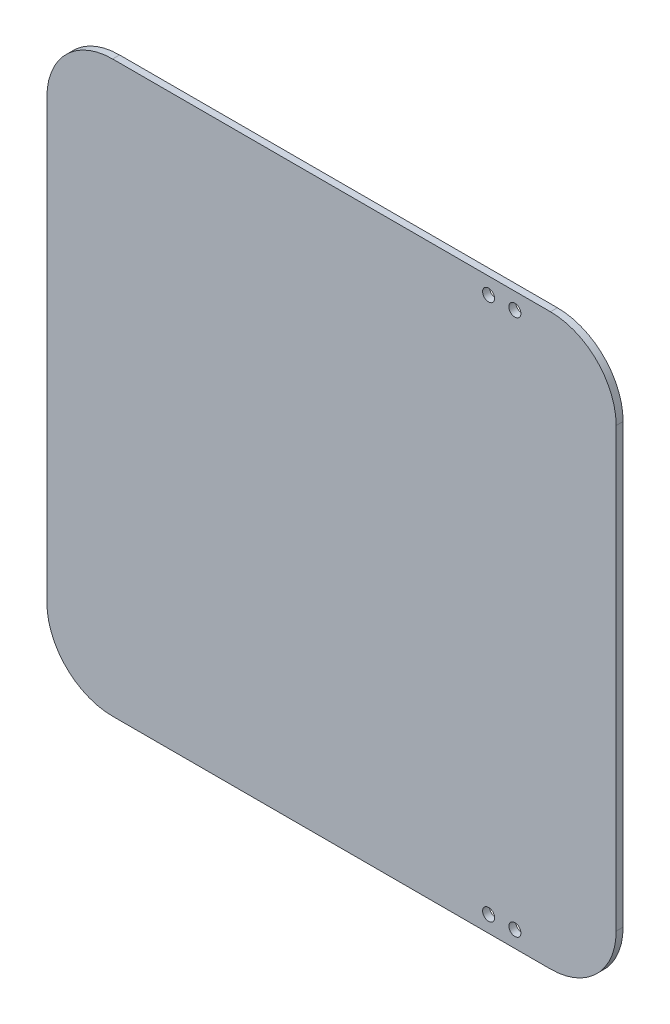
SolidWorks part; units mm, degrees
ref_plane "Front Plane" through (0, 0, 0) normal (0, 0, 1) x (1, 0, 0)
ref_plane "Top Plane" through (0, 0, 0) normal (0, 1, 0) x (1, 0, 0)
ref_plane "Right Plane" through (0, 0, 0) normal (1, 0, 0) x (0, 0, -1)
sketch "Sketch1" plane through (0, 0, 0) normal (0, 0, 1) x (1, 0, 0)
  line L4 (79.7168, 314.2679) -> (-120.2832, 314.2679)
  line L5 (109.7168, 84.2679) -> (109.7168, 284.2679)
  line L6 (-120.2832, 54.2679) -> (79.7168, 54.2679)
  line L7 (-150.2832, 284.2679) -> (-150.2832, 84.2679)
  arc A4 (-120.2832, 314.2679) -> (-150.2832, 284.2679) centre (-120.2832, 284.2679) ccw
  arc A5 (109.7168, 284.2679) -> (79.7168, 314.2679) centre (79.7168, 284.2679) ccw
  arc A6 (79.7168, 54.2679) -> (109.7168, 84.2679) centre (79.7168, 84.2679) ccw
  arc A7 (-150.2832, 84.2679) -> (-120.2832, 54.2679) centre (-120.2832, 84.2679) ccw
extrude "Boss-Extrude1" add sketch "Sketch1" against normal blind 3.175 contours L4 A4 L7 A7 L6 A6 L5 A5
sketch "Sketch2" plane through (0, 0, 0) normal (0, 0, 1) x (1, 0, 0)
  circle A0 centre (51.4668, 306.7679) radius 2.75 construction
  circle A1 centre (63.4668, 306.7679) radius 2.75 construction
  circle A2 centre (51.4668, 306.7679) radius 2.75
  circle A3 centre (63.4668, 306.7679) radius 2.75
  circle A4 centre (63.4668, 61.7679) radius 2.75 construction
  circle A5 centre (51.4668, 61.7679) radius 2.75 construction
  circle A6 centre (63.4668, 61.7679) radius 2.75
  circle A7 centre (51.4668, 61.7679) radius 2.75
extrude "Cut-Extrude1" cut sketch "Sketch2" against normal through all
